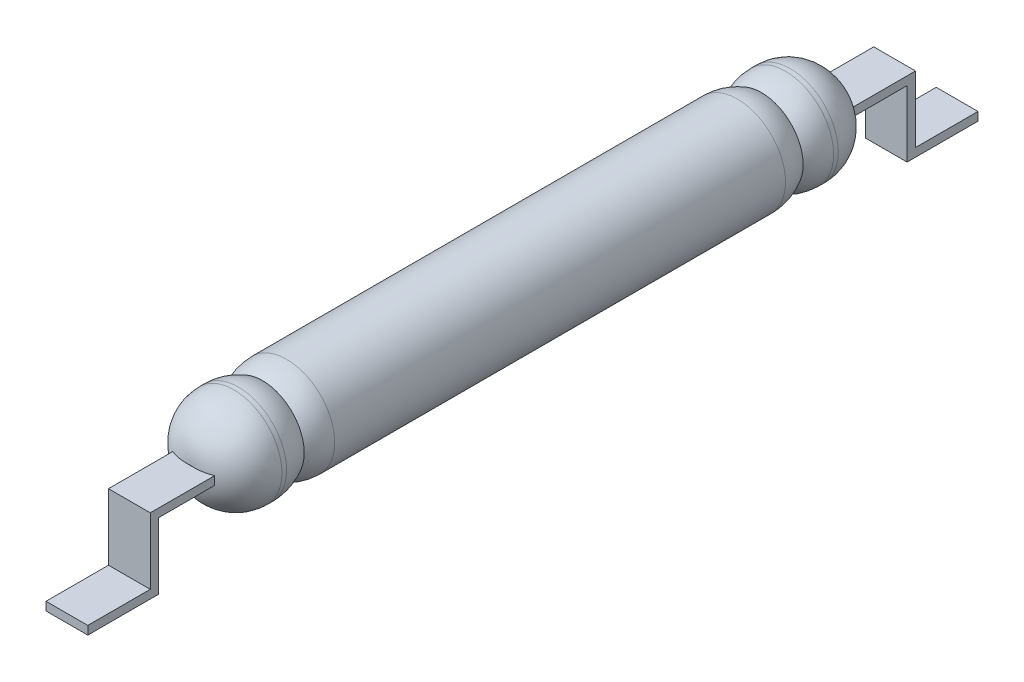
SolidWorks part; units mm, degrees
ref_plane "Front Plane" through (0, 0, 0) normal (0, 0, 1) x (1, 0, 0)
ref_plane "Top Plane" through (0, 0, 0) normal (0, 1, 0) x (1, 0, 0)
ref_plane "Right Plane" through (0, 0, 0) normal (1, 0, 0) x (0, 0, -1)
ref_plane "Plane1"
sketch "Sketch1" plane through (0, 0, 0) normal (0, 0, 1) x (1, 0, 0)
  circle A0 centre (0, 0) radius 1.14
  dimension "D1" = 2.28
extrude "Extrusion1" add sketch "Sketch1" along normal blind 15.24
ref_plane "Plane2" through (0, 0, 0) normal (1, 0, 0) x (0, 1, 0)
ref_plane "Plane3" through (0, 0, 7.62) normal (0, 0, 1) x (1, 0, 0)
ref_plane "Plane4" through (0, 0, 0) normal (1, 0, 0) x (0, 1, 0)
sketch "Sketch3" plane through (0, 0, 0) normal (1, 0, 0) x (0, 1, 0)
  line L0 (1.14, 12.96) -> (1.14, 14.1)
  line L1 (0, 14.1) -> (0, 12.96) construction
  arc A0 (0.9873, 13.53) -> (1.14, 14.1) centre (0, 14.1) ccw
  arc A1 (1.14, 12.96) -> (0.9873, 13.53) centre (0, 12.96) ccw
revolve "Revolution3" cut sketch "Sketch3" angle 360 about L1
ref_plane "Plane5" through (0, 0, 7.62) normal (0, 0, 1) x (1, 0, 0)
mirror "Mirror2" about plane through (0, 0, 7.62) normal (0, 0, 1) of "Revolution3"
ref_plane "Plane6" through (0, 0, 0) normal (1, 0, 0) x (0, 1, 0)
sketch "Sketch4" plane through (0, 0, 0) normal (1, 0, 0) x (0, 1, 0)
  line L0 (0.1, 0) -> (0.1, 0.1388)
  line L1 (0.1, 0.1388) -> (-0.1, 0.1388)
  line L2 (-0.1, 0.1388) -> (-0.1, 0)
  line L3 (-0.1, 0) -> (0.1, 0)
  line L4 (-0.1, 0.0044) -> (-0.1, -1.245)
  line L5 (-0.1, -1.245) -> (-1.67, -1.245)
  line L6 (-1.67, -1.245) -> (-1.67, -2.925)
  line L7 (-1.67, -2.925) -> (-1.47, -2.925)
  line L8 (-1.47, -2.925) -> (-1.47, -1.445)
  line L9 (-1.47, -1.445) -> (0.1, -1.445)
  line L10 (0.1, -1.445) -> (0.1, 0.0044)
  arc A0 (-0.1, 0.0044) -> (0, 0) centre (0, 1.14) ccw
  arc A1 (0, 0) -> (0.1, 0.0044) centre (0, 1.14) ccw
extrude "Extrusion2" add sketch "Sketch4" along normal blind 0.495 and the other way blind 0.495 contours A0 L2 L3 | A0 A1 L0 L1 L2 | L9 L10 L3 L4 L5 L6 L7 L8 region at (0, -0.826, -1.4215) region at (0, 0, 0.0701) region at (0, -0.075, 0.0013)
ref_plane "Plane7" through (0, 0, 7.62) normal (0, 0, 1) x (1, 0, 0)
mirror "Mirror3" about plane through (0, 0, 7.62) normal (0, 0, 1) of "Extrusion2"
fillet "Fillet3" radius 1.03 2 edges at (1.14, 0, 15.24) (1.14, 0, 0)
